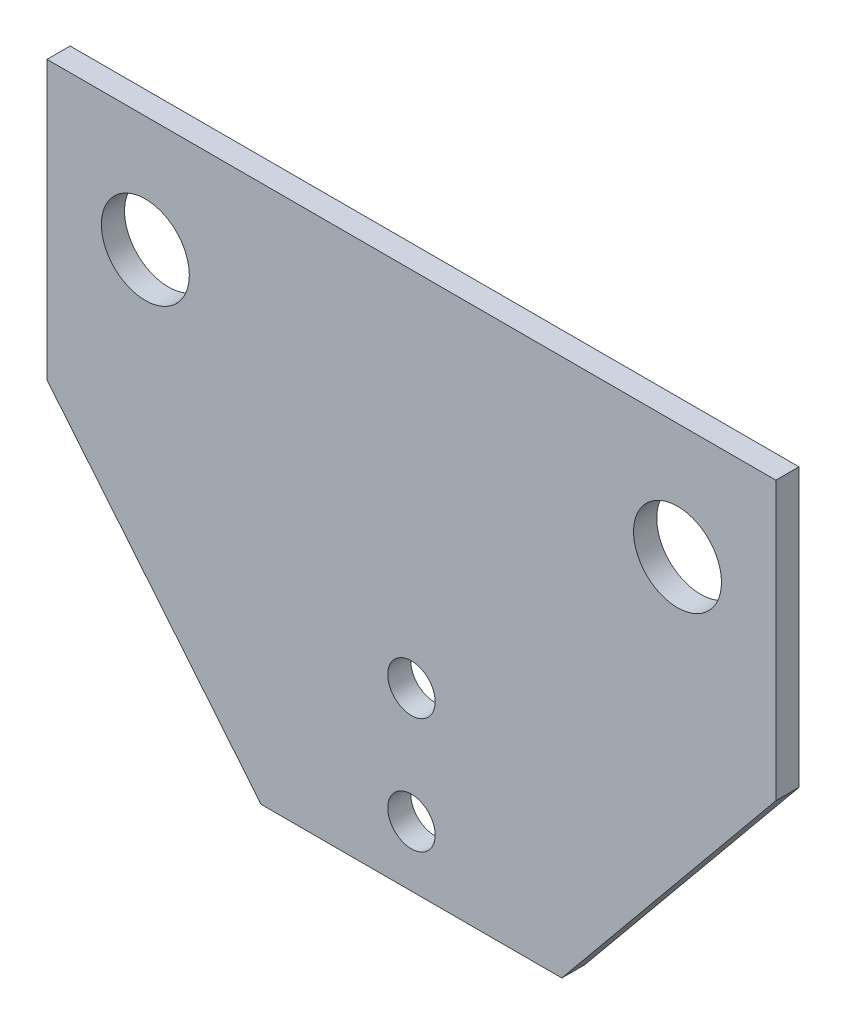
SolidWorks part; units mm, degrees
ref_plane "Front Plane" through (0, 0, 0) normal (0, 0, 1) x (1, 0, 0)
ref_plane "Top Plane" through (0, 0, 0) normal (0, 1, 0) x (1, 0, 0)
ref_plane "Right Plane" through (0, 0, 0) normal (1, 0, 0) x (0, 0, -1)
sketch "Sketch1" plane through (0, 0, 0) normal (0, 0, 1) x (1, 0, 0)
  line L0 (0, 0) -> (0, 60.5723) construction
  line L1 (0, -55) -> (0, 55) construction
  line L2 (55, 0) -> (-55, 0) construction
  line L3 (31.5, 10) -> (-31.5, 10)
  line L4 (-31.5, 10) -> (-31.5, -14)
  line L5 (-31.5, -14) -> (31.5, -14)
  line L6 (31.5, 10) -> (31.5, -14)
  line L7 (0, -36.5157) -> (-13, -36.5157)
  line L8 (0, -36.5157) -> (13, -36.5157)
  line L9 (-13, -36.5157) -> (-31.5, -14)
  line L10 (13, -36.5157) -> (31.5, -14)
  circle A0 centre (-23, 0) radius 3.3
  circle A1 centre (-23, 0) radius 3.8
  circle A2 centre (23, 0) radius 3.3
  circle A3 centre (23, 0) radius 3.8
  circle A4 centre (0, -21.3221) radius 2.05
  circle A5 centre (0, -31.3) radius 2.05
  point P5 (-23, 0)
  point P6 (23, 0)
  point P12 (0, -36.5157)
  point P17 (0, -14)
  point P21 (0, 10)
  dimension "D3" = 10
  dimension "D7" = 6.6
  dimension "D8" = 7.6
  dimension "D9" = 4.1
  dimension "D10" = 4.1
  dimension "D1" = 23
  dimension "D2" = 23
  dimension "D4" = 63
  dimension "D5" = 24
  dimension "D6" = 13
extrude "Boss-Extrude1" add sketch "Sketch1" along normal blind 2 contours L6 L3 L4 L5 A1 A3 region at (0, -2.1277, 0)
extrude "Boss-Extrude2" add sketch "Sketch1<3>" along normal blind 2 contours L8 L10 L5 L9 L7 A5 A4 region at (0, -23.627, 0)
sketch "Sketch1<3>" plane through (0, 0, 0) normal (0, 0, 1) x (1, 0, 0) same geometry as "Sketch1"
